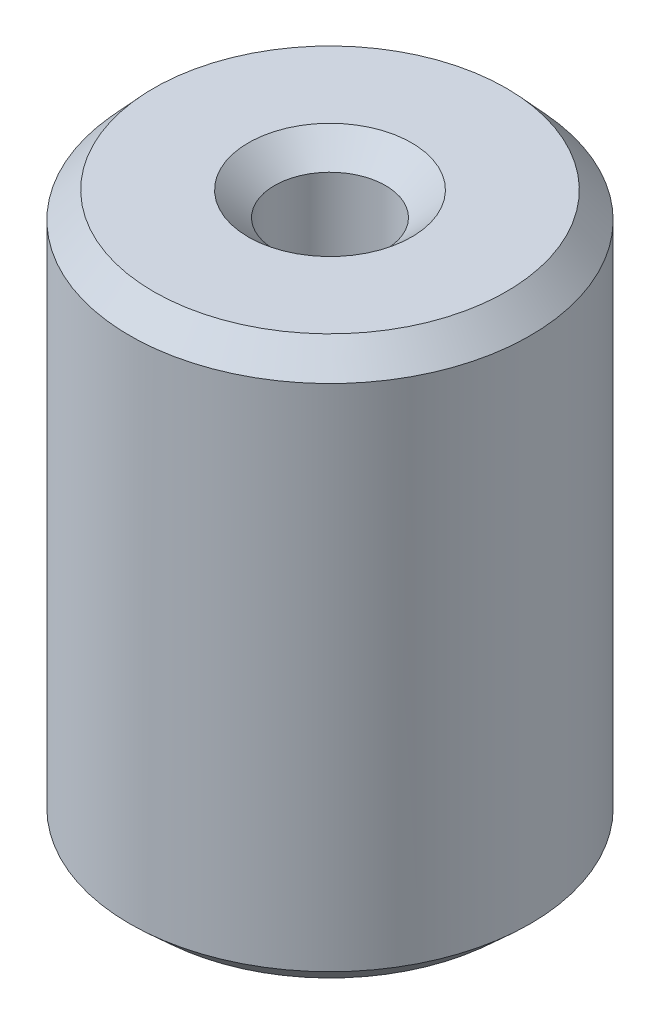
SolidWorks part; units mm, degrees
ref_plane "Front Plane" through (0, 0, 0) normal (0, 0, 1) x (1, 0, 0)
ref_plane "Top Plane" through (0, 0, 0) normal (0, 1, 0) x (1, 0, 0)
ref_plane "Right Plane" through (0, 0, 0) normal (1, 0, 0) x (0, 0, -1)
sketch "Sketch1" plane through (0, 0, 0) normal (0, 1, 0) x (1, 0, 0)
  circle A0 centre (0, 0) radius 5
  dimension "SLEEVE_OD" = 10
extrude "Boss-Extrude1" add sketch "Sketch1" along normal blind 13.9698
sketch "Sketch2" plane through (0, 0, 0) normal (0, 1, 0) x (1, 0, 0)
  circle A0 centre (0, 0) radius 1.3864
  dimension "BORE_D" = 2.7728
extrude "Cut-Extrude1" cut sketch "Sketch2" along normal through all
chamfer "Chamfer1" distance 0.6525 angle 42.482 4 edges at (0, 13.9698, 1.3864) (0, 0, 1.3864) (0, 0, 5) (0, 13.9698, 5) first distance on face at (0, 13.9698, 1.3864) first distance on face at (0, 0, 1.3864) first distance on face at (0, 13.9698, 5)
